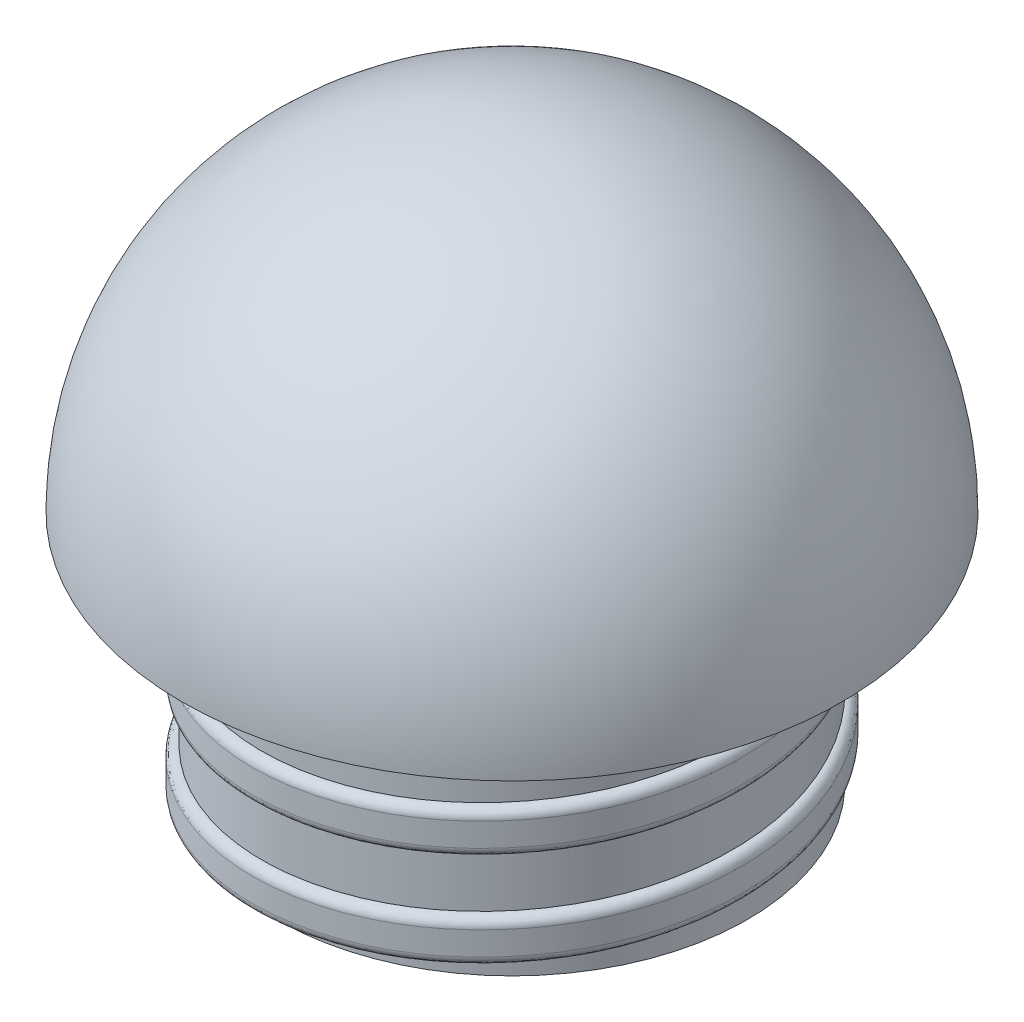
SolidWorks part; units mm, degrees
ref_plane "Front Plane" through (0, 0, 0) normal (0, 0, 1) x (1, 0, 0)
ref_plane "Top Plane" through (0, 0, 0) normal (0, 1, 0) x (1, 0, 0)
ref_plane "Right Plane" through (0, 0, 0) normal (1, 0, 0) x (0, 0, -1)
sketch "Sketch1" plane through (0, 0, 0) normal (0, 1, 0) x (1, 0, 0)
  line L0 (-7, 0) -> (7, 0)
  arc A1 (7, 0) -> (-7, 0) centre (0, 0) ccw
revolve "Revolve1" add sketch "Sketch1" angle 180 about L0
sketch "Sketch2" plane through (0, 0, 0) normal (0, -1, 0) x (-1, 0, 0)
  circle A0 centre (0, 0) radius 5
extrude "Boss-Extrude1" add sketch "Sketch2" along normal blind 5 contours A0
sketch "Sketch3" plane through (0, -5, 0) normal (0, -1, 0) x (-1, 0, 0)
  circle A0 centre (0, 0) radius 5
curve "Helix/Spiral1" pitch 2 height 5 radius 5 centre (0, -5, 0) axis (0, 1, 0) start towards (0, 0, -1)
ref_plane "Plane1" through (-5, -5, 0) normal (0, 0.0635, 0.998) x (1, 0, 0)
sketch "Sketch4" plane through (-5, -5, 0) normal (0, 0.0635, 0.998) x (1, 0, 0)
  line L0 (0, -0.25) -> (0, 0.25) construction
  line L1 (-0.2, -0.25) -> (-0.2, 0.25)
  line L2 (0.2, -0.25) -> (0.2, 0.25)
  arc A0 (-0.2, -0.25) -> (0.2, -0.25) centre (0, -0.25) ccw
  arc A1 (0.2, 0.25) -> (-0.2, 0.25) centre (0, 0.25) ccw
  point P2 (0, 0)
  dimension "D1" = 0.5
  dimension "D2" = 0.2
sweep "Sweep1" add profiles "Sketch4" path "Helix/Spiral1"
ref_plane "Plane2" through (0, 0, 10) normal (0, 0, 1) x (1, 0, 0)
sketch "Sketch5" plane through (0, 0, 10) normal (0, 0, 1) x (1, 0, 0)
  line L1 (-19.5679, -6.4814) -> (5, -6.4814)
  line L2 (-19.5679, -6.4814) -> (-19.5679, -5)
  line L3 (-19.5679, -5) -> (5, -5)
  line L4 (5, -6.4814) -> (5, -5)
  line L5 (-19.5679, -6.4814) -> (5, -5) construction
  line L6 (-19.5679, -5) -> (5, -6.4814) construction
  point P0 (-7.2839, -5.7407)
extrude "Cut-Extrude1" cut sketch "Sketch5" against normal blind 25
